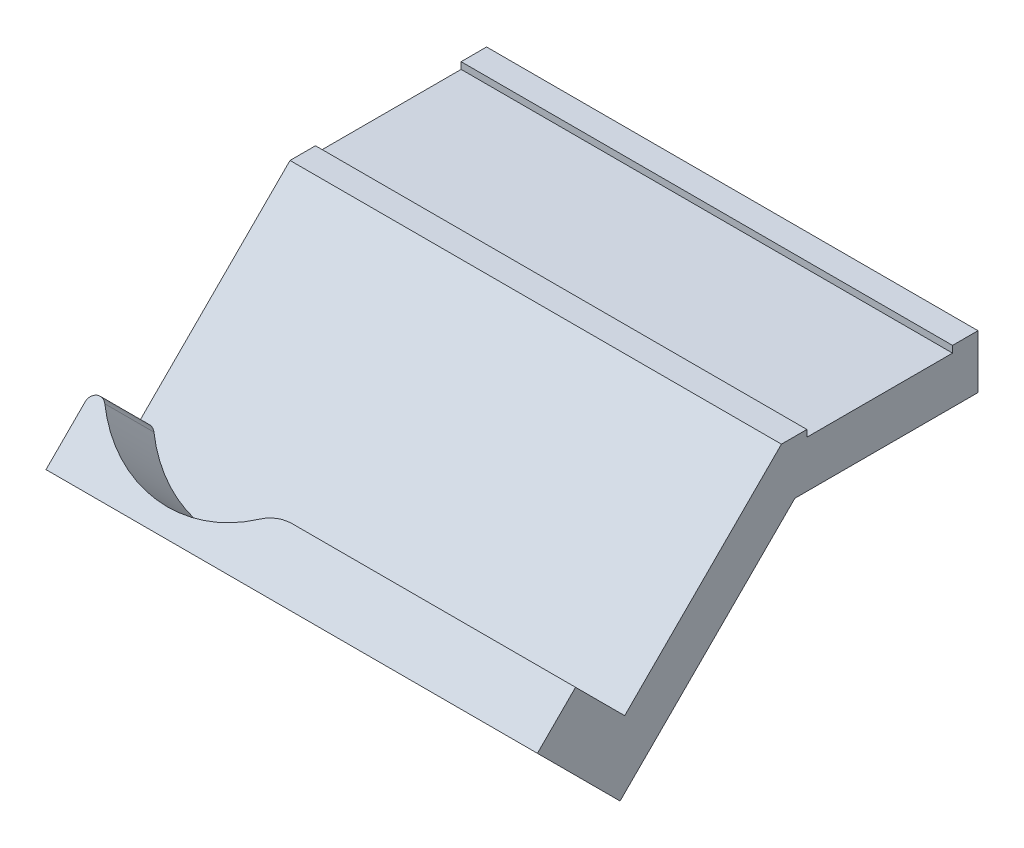
SolidWorks part; units mm, degrees
ref_plane "Front Plane" through (0, 0, 0) normal (0, 0, 1) x (1, 0, 0)
ref_plane "Top Plane" through (0, 0, 0) normal (0, 1, 0) x (1, 0, 0)
ref_plane "Right Plane" through (0, 0, 0) normal (1, 0, 0) x (0, 0, -1)
sketch "Sketch1" plane through (0, 0, 0) normal (0, 1, 0) x (1, 0, 0)
  line L1 (0, 30.75) -> (55, 30.75)
  line L2 (0, 30.75) -> (0, 0)
  line L3 (0, 0) -> (55, 0)
  line L4 (55, 30.75) -> (55, 0)
  dimension "D1" = 55
  dimension "D2" = 30.75
extrude "Boss-Extrude1" add sketch "Sketch1" along normal blind 50 contours L2 L3 L4 L1
sketch "Sketch4" plane through (55, 0, 0) normal (1, 0, 0) x (0, 0, -1)
  line L0 (30.75, 0) -> (0, 0) construction
  line L1 (-27.3553, 45.3553) -> (8, 80.7107)
  line L2 (-27.3553, 45.3553) -> (8, 10)
  line L3 (8, 10) -> (43.3553, 45.3553)
  line L4 (8, 80.7107) -> (43.3553, 45.3553)
  line L5 (0, 50) -> (0, 0) construction
  dimension "D1" = 50
  dimension "D2" = 50
  dimension "D3" = 10
  dimension "D4" = 8
  dimension "D5" = 45
extrude "Cut-Extrude1" cut sketch "Sketch4" against normal blind 50
sketch "Sketch5" plane through (55, 0, 0) normal (1, 0, 0) x (0, 0, -1)
  line L0 (0, 18) -> (0, 0) construction
  line L1 (-11.6421, 15.5) -> (-4.5711, 22.5711)
  line L2 (-11.6421, 15.5) -> (-4.5711, 8.4289)
  line L3 (-4.5711, 8.4289) -> (2.5, 15.5)
  line L4 (-4.5711, 22.5711) -> (2.5, 15.5)
  line L5 (0, 18) -> (8, 10) construction
  dimension "D1" = 10
  dimension "D2" = 10
  dimension "D3" = 2.5
extrude "Cut-Extrude2" cut sketch "Sketch5" against normal through all
sketch "Sketch12" plane through (55, 0, 0) normal (1, 0, 0) x (0, 0, -1)
  line L0 (2.5, 15.5) -> (8, 10)
  line L1 (8, 10) -> (8.7071, 10.7071)
  line L2 (8, 10) -> (30.75, 32.75) construction
  line L3 (8.7071, 10.7071) -> (3.2071, 16.2071)
  line L4 (3.2071, 16.2071) -> (2.5, 15.5)
  dimension "D1" = 1
extrude "Boss-Extrude2" add sketch "Sketch12" against normal through all contours L3 L4 L0 L1
sketch "Sketch6" plane through (0, 1, 1) normal (0, 0.7071, 0.7071) x (1, 0, 0)
  line L0 (55, 9.1924) -> (0, 9.1924) construction
  line L3 (0, 57.0989) -> (0, 35.3553) construction
  circle A0 centre (12, 23.6924) radius 13.75
  dimension "D1" = 27.5
  dimension "D2" = 14.5
  dimension "D3" = 12
extrude "Cut-Extrude3" cut sketch "Sketch6" along normal through all
ref_axis "Axis2" through (12, 37.8672, 4.3611) along (0, -0.7071, -0.7071)
sketch "Sketch7" plane through (55, 0, 0) normal (1, 0, 0) x (0, 0, -1)
  line L0 (0, 13) -> (5.5063, 18.5063)
  line L1 (20.4998, 22.4998) -> (11.0063, 13.0063) construction
  line L2 (5.5063, 18.5063) -> (11.0063, 13.0063)
  line L3 (11.0063, 13.0063) -> (61, 63)
  line L4 (61, 63) -> (25.4084, 63)
  line L5 (25.4084, 63) -> (0, 63)
  line L6 (0, 63) -> (0, 13)
  line L7 (11.0063, 13.0063) -> (0, 24.0127) construction
  line L8 (8.7071, 10.7071) -> (30.75, 32.75) construction
  dimension "D1" = 50
extrude "Cut-Extrude4" cut sketch "Sketch7" against normal through all contours L5 L6 L0 L2 L3 L4
sketch "Sketch8" plane through (0, 0, 0) normal (0, 1, 0) x (1, 0, 0)
  line L0 (12, -4.3611) -> (12, 12.0686) construction
  line L3 (55, 30.75) -> (0, 30.75) construction
  circle A0 centre (25.75, 32.25) radius 6
  dimension "D1" = 12
  dimension "D3" = 1.5
  dimension "D2" = 13.75
extrude "Cut-Extrude5" cut sketch "Sketch8" along normal through all contours A0
sketch "Sketch9" plane through (55, 0, 0) normal (1, 0, 0) x (0, 0, -1)
  line L0 (26.25, 28.25) -> (30.75, 28.25)
  line L1 (30.75, 32.75) -> (30.75, 0) construction
  line L2 (30.75, 28.25) -> (30.75, 32.75)
  line L3 (30.75, 32.75) -> (26.25, 28.25)
extrude "Cut-Extrude6" cut sketch "Sketch9" against normal through all
sketch "Sketch10" plane through (0, 0, 0) normal (0, 1, 0) x (1, 0, 0)
  line L0 (0, 26.25) -> (25.75, 26.25) construction
  line L1 (55, 26.25) -> (0, 26.25)
  line L2 (55, 26.25) -> (55, 30.75)
  line L3 (55, 30.75) -> (0, 30.75)
  line L4 (0, 26.25) -> (0, 30.75)
  line L5 (0, 26.25) -> (0, 11.0063) construction
extrude "Cut-Extrude7" cut sketch "Sketch10" along normal through all
fillet "Fillet5" radius 1 1 edges at (0, 15.7563, -8.2563) tangent propagation no
fillet "Fillet6" radius 5 1 edges at (21.4748, 13.4571, -5.9571)
sketch "Sketch16" plane through (55, 0, 0) normal (1, 0, 0) x (0, 0, -1)
  line L0 (26.25, 20.75) -> (9.25, 3.75)
  line L1 (26.25, 28.25) -> (26.25, 0) construction
  line L2 (9.25, 3.75) -> (0, 13)
  line L3 (0, 13) -> (0, 0)
  line L4 (0, 0) -> (26.25, 0)
  line L5 (26.25, 0) -> (26.25, 20.75)
  line L6 (8.7071, 10.7071) -> (26.25, 28.25) construction
  line L7 (26.25, 0) -> (0, 0) construction
  dimension "D1" = 7.5
extrude "Cut-Extrude8" cut sketch "Sketch16" against normal through all
sketch "Sketch17" plane through (0, 0, -26.25) normal (0, 0, -1) x (-1, 0, 0)
  line L1 (-55, 28.25) -> (0, 28.25)
  line L2 (-55, 28.25) -> (-55, 22.25)
  line L3 (-55, 22.25) -> (0, 22.25)
  line L4 (0, 28.25) -> (0, 22.25)
  dimension "D1" = 6
extrude "Boss-Extrude4" add sketch "Sketch17" along normal blind 22
sketch "Sketch18" plane through (55, 0, 0) normal (1, 0, 0) x (0, 0, -1)
  line L0 (17.75, 12.25) -> (33.75, 28.25)
  line L1 (26.25, 20.75) -> (9.25, 3.75) construction
  line L2 (48.25, 28.25) -> (26.25, 28.25) construction
  line L3 (33.75, 28.25) -> (26.25, 28.25)
  line L4 (26.25, 28.25) -> (14, 16)
  line L5 (8.7071, 10.7071) -> (26.25, 28.25) construction
  line L6 (14, 16) -> (17.75, 12.25)
extrude "Boss-Extrude5" add sketch "Sketch18" against normal up to surface (55 mm away) contours L0 L3 L4 L6 up to face at (0, 18.4844, -23.0677)
sketch "Sketch19" plane through (0, 28.25, 0) normal (0, 1, 0) x (1, 0, 0)
  line L0 (0, 48.25) -> (0, 26.25) construction
  line L1 (0, 45.4) -> (55, 45.4)
  line L2 (0, 45.4) -> (0, 29.1)
  line L3 (0, 29.1) -> (55, 29.1)
  line L4 (55, 45.4) -> (55, 29.1)
  line L5 (55, 48.25) -> (55, 26.25) construction
  point P8 (0, 37.25)
  dimension "D1" = 16.3
extrude "Cut-Extrude9" cut sketch "Sketch19" against normal blind 0.75
sketch "Sketch20" plane through (55, 0, 0) normal (1, 0, 0) x (0, 0, -1)
  line L0 (0, 13) -> (-1.0607, 11.9393)
  line L1 (-1.0607, 11.9393) -> (8.1893, 2.6893)
  line L2 (8.1893, 2.6893) -> (9.25, 3.75)
  line L3 (9.25, 3.75) -> (0, 13)
  line L4 (0, 13) -> (3.2071, 16.2071) construction
  line L5 (27.75, 22.25) -> (9.25, 3.75) construction
  dimension "D1" = 1.5
extrude "Boss-Extrude6" add sketch "Sketch20" against normal up to surface (55 mm away) contours L1 L2 L3 L0 up to face at (0, 21.3633, -27.5924)
